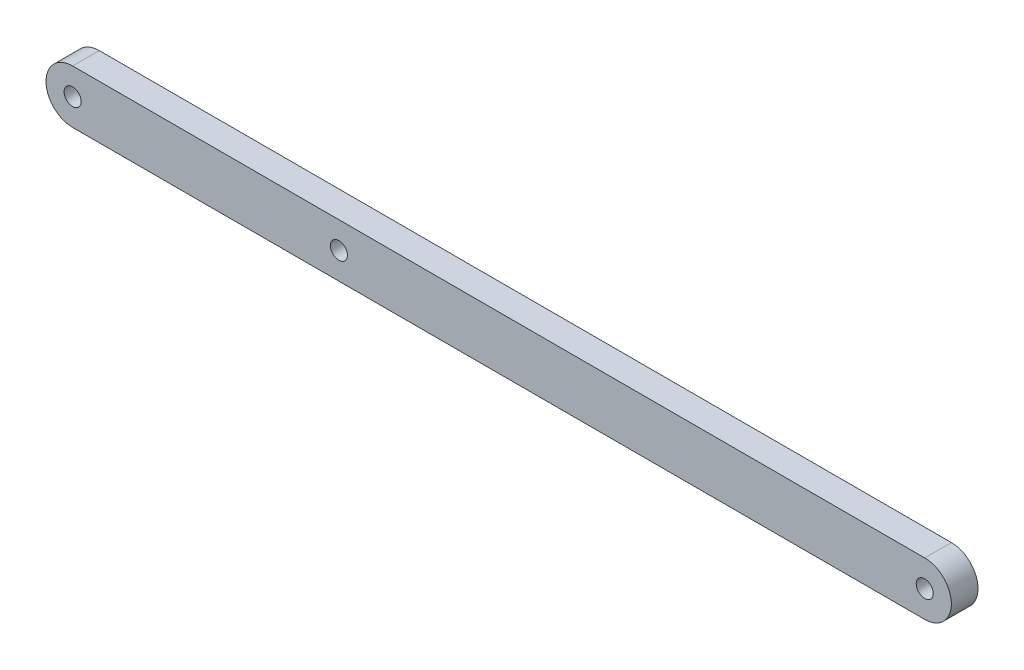
SolidWorks part; units mm, degrees
ref_plane "Front Plane" through (0, 0, 0) normal (0, 0, 1) x (1, 0, 0)
ref_plane "Top Plane" through (0, 0, 0) normal (0, 1, 0) x (1, 0, 0)
ref_plane "Right Plane" through (0, 0, 0) normal (1, 0, 0) x (0, 0, -1)
sketch "Sketch2" plane through (0, 0, 0) normal (0, 0, 1) x (1, 0, 0)
  line L0 (0, 0) -> (203.2, 0) construction
  line L1 (0, 6.35) -> (203.2, 6.35)
  line L2 (0, -6.35) -> (203.2, -6.35)
  arc A0 (0, 6.35) -> (0, -6.35) centre (0, 0) ccw
  arc A1 (203.2, -6.35) -> (203.2, 6.35) centre (203.2, 0) ccw
  circle A2 centre (0, 0) radius 2.032
  circle A3 centre (203.2, 0) radius 2.032
  circle A4 centre (63.5, 0) radius 2.032
  point P3 (101.6, 0)
  dimension "D3" = 4.064
  dimension "D4" = 63.5
  dimension "D5" = 4.064
  dimension "D1" = 203.2
  dimension "D2" = 12.7
extrude "Boss-Extrude1" add sketch "Sketch2" along normal mid plane 6.35
